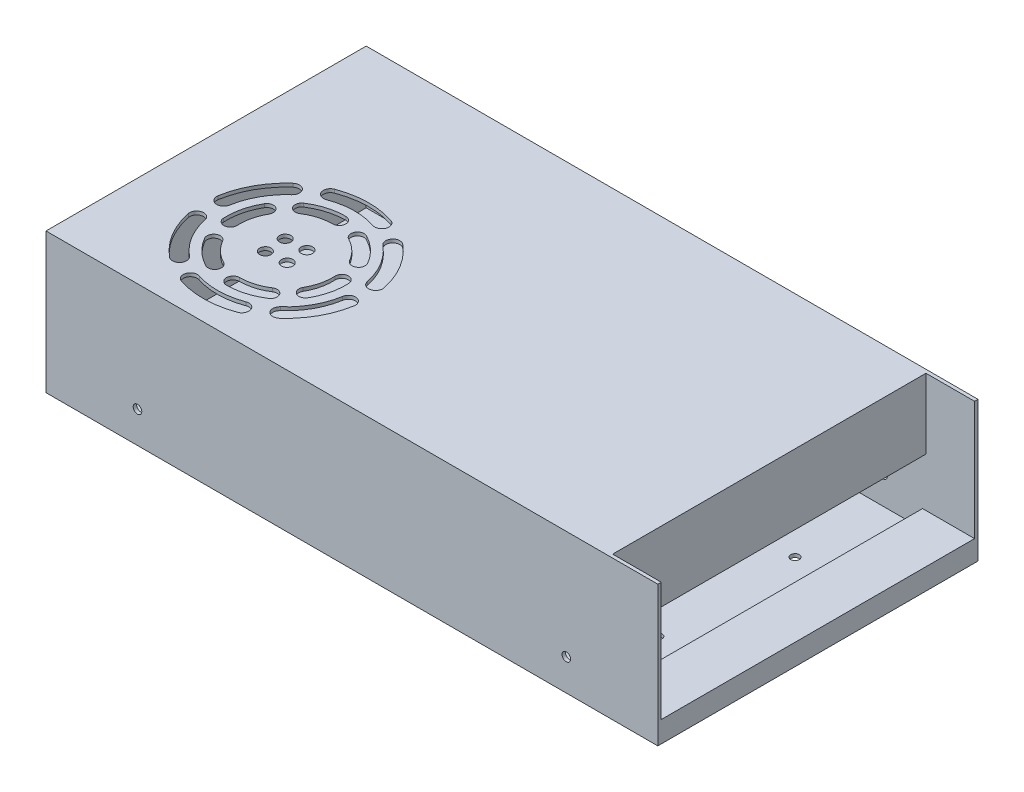
SolidWorks part; units mm, degrees
ref_plane "Front Plane" through (0, 0, 0) normal (0, 0, 1) x (1, 0, 0)
ref_plane "Top Plane" through (0, 0, 0) normal (0, 1, 0) x (1, 0, 0)
ref_plane "Right Plane" through (0, 0, 0) normal (1, 0, 0) x (0, 0, -1)
sketch "Sketch1" plane through (0, 0, 0) normal (0, 1, 0) x (1, 0, 0)
  line L1 (-107, 56) -> (107, 56)
  line L2 (-107, 56) -> (-107, -56)
  line L3 (-107, -56) -> (107, -56)
  line L4 (107, 56) -> (107, -56)
  line L5 (-107, 56) -> (107, -56) construction
  line L6 (-107, -56) -> (107, 56) construction
  point P0 (0, 0)
  dimension "D1" = 214
  dimension "D2" = 112
extrude "Boss-Extrude1" add sketch "Sketch1" along normal blind 49
sketch "Sketch2" plane through (0, 49, 0) normal (0, 1, 0) x (1, 0, 0)
  line L0 (107, -56) -> (107, 56) construction
  line L1 (107, 54.8) -> (88.8, 54.8)
  line L2 (107, 54.8) -> (107, -54.8)
  line L3 (107, -54.8) -> (88.8, -54.8)
  line L4 (88.8, 54.8) -> (88.8, -54.8)
  line L5 (107, 56) -> (-107, 56) construction
  line L6 (-107, -56) -> (107, -56) construction
  dimension "D1" = 18.2
  dimension "D2" = 1.2
  dimension "D3" = 1.2
extrude "Cut-Extrude1" cut sketch "Sketch2" against normal offset from surface (41.6 mm away) 7.4 up to face at (0, 0, 0)
shell "Shell1" thickness 1.2 removed face at (88.8, 28.2, 0)
sketch "Sketch3" plane through (0, 0, 56) normal (0, 0, 1) x (1, 0, 0)
  line L0 (-107, 0) -> (107, 0) construction
  line L1 (107, 49) -> (107, 0) construction
  line L3 (-107, 49) -> (-107, 0) construction
  circle A0 centre (75, 11) radius 1.5
  circle A1 centre (-75, 11) radius 1.5
  dimension "D1" = 3
  dimension "D4" = 3
  dimension "D2" = 11
  dimension "D3" = 32
  dimension "D5" = 11
  dimension "D6" = 32
extrude "Cut-Extrude2" cut sketch "Sketch3" against normal blind 10
sketch "Sketch4" plane through (0, 0, -56) normal (0, 0, -1) x (-1, 0, 0)
  line L0 (-107, 0) -> (107, 0) construction
  line L1 (-107, 49) -> (-107, 0) construction
  line L2 (107, 49) -> (107, 0) construction
  line L3 (-107, 49) -> (107, 49) construction
  circle A0 centre (-75, 11) radius 1.5
  circle A1 centre (-75, 36) radius 1.5
  circle A2 centre (75, 36) radius 1.5
  circle A3 centre (75, 11) radius 1.5
  dimension "D2" = 3
  dimension "D4" = 32
  dimension "D6" = 3
  dimension "D11" = 3
  dimension "D12" = 3
  dimension "D1" = 11
  dimension "D3" = 32
  dimension "D5" = 11
  dimension "D7" = 13
  dimension "D8" = 32
  dimension "D9" = 13
  dimension "D10" = 32
extrude "Cut-Extrude3" cut sketch "Sketch4" against normal blind 10
sketch "Sketch5" plane through (88.8, 0, 0) normal (1, 0, 0) x (0, 0, -1)
  line L0 (54.8, 47.8) -> (54.8, 1.2) construction
  line L1 (-54.8, 49) -> (54.8, 49)
  line L2 (-54.8, 49) -> (-54.8, 24.5)
  line L3 (-54.8, 24.5) -> (54.8, 24.5)
  line L4 (54.8, 49) -> (54.8, 24.5)
extrude "Boss-Extrude2" add sketch "Sketch5" along normal blind 1.2
sketch "Sketch6" plane through (0, 49, 0) normal (0, 1, 0) x (1, 0, 0)
  line L0 (-107, -56) -> (107, -56) construction
  line L1 (-107, 56) -> (-107, -56) construction
  arc A3 (-67.3347, -45.1552) -> (-49.6905, -44.8109) centre (-59, -20) ccw construction
  arc A4 (-68.1117, -47.5004) -> (-48.8226, -47.1241) centre (-59, -20) ccw
  arc A5 (-66.5576, -42.8099) -> (-50.5584, -42.4978) centre (-59, -20) ccw
  arc A6 (-66.5576, -42.8099) -> (-68.1117, -47.5004) centre (-67.3347, -45.1552) ccw
  arc A7 (-48.8226, -47.1241) -> (-50.5584, -42.4978) centre (-49.6905, -44.8109) ccw
  arc A8 (-84.9529, -25.3601) -> (-75.8327, -40.4682) centre (-59.0005, -20.0005) ccw construction
  arc A9 (-87.3725, -25.8597) -> (-77.402, -42.3765) centre (-59.0005, -20.0005) ccw
  arc A10 (-82.5333, -24.8604) -> (-74.2634, -38.56) centre (-59.0005, -20.0005) ccw
  arc A11 (-82.5333, -24.8604) -> (-87.3725, -25.8597) centre (-84.9529, -25.3601) ccw
  arc A12 (-77.402, -42.3765) -> (-74.2634, -38.56) centre (-75.8327, -40.4682) ccw
  arc A13 (-76.6189, -0.2046) -> (-85.1429, -15.657) centre (-59.0012, -20.0003) ccw construction
  arc A14 (-78.2614, 1.6409) -> (-87.5801, -15.2521) centre (-59.0012, -20.0003) ccw
  arc A15 (-74.9764, -2.0502) -> (-82.7057, -16.062) centre (-59.0012, -20.0003) ccw
  arc A16 (-74.9764, -2.0502) -> (-78.2614, 1.6409) centre (-76.6189, -0.2046) ccw
  arc A17 (-87.5801, -15.2521) -> (-82.7057, -16.062) centre (-85.1429, -15.657) ccw
  arc A18 (-50.6667, 5.1556) -> (-68.3109, 4.8114) centre (-59.0014, -19.9996) ccw construction
  arc A19 (-49.8897, 7.5009) -> (-69.1788, 7.1246) centre (-59.0014, -19.9996) ccw
  arc A20 (-51.4438, 2.8104) -> (-67.4429, 2.4982) centre (-59.0014, -19.9996) ccw
  arc A21 (-51.4438, 2.8104) -> (-49.8897, 7.5009) centre (-50.6667, 5.1556) ccw
  arc A22 (-69.1788, 7.1246) -> (-67.4429, 2.4982) centre (-68.3109, 4.8114) ccw
  arc A23 (-33.0485, -14.6395) -> (-42.1687, 0.4687) centre (-59.0008, -19.9991) ccw construction
  arc A24 (-30.6289, -14.1398) -> (-40.5994, 2.3769) centre (-59.0008, -19.9991) ccw
  arc A25 (-35.468, -15.1392) -> (-43.738, -1.4396) centre (-59.0008, -19.9991) ccw
  arc A26 (-35.468, -15.1392) -> (-30.6289, -14.1398) centre (-33.0485, -14.6395) ccw
  arc A27 (-40.5994, 2.3769) -> (-43.738, -1.4396) centre (-42.1687, 0.4687) ccw
  arc A28 (-41.3824, -39.7949) -> (-32.8585, -24.3425) centre (-59.0001, -19.9993) ccw construction
  arc A29 (-39.7399, -41.6405) -> (-30.4213, -24.7474) centre (-59.0001, -19.9993) ccw
  arc A30 (-43.025, -37.9493) -> (-35.2957, -23.9376) centre (-59.0001, -19.9993) ccw
  arc A31 (-43.025, -37.9493) -> (-39.7399, -41.6405) centre (-41.3824, -39.7949) ccw
  arc A32 (-30.4213, -24.7474) -> (-35.2957, -23.9376) centre (-32.8585, -24.3425) ccw
  arc A34 (-59.0008, -38.56) -> (-48.8989, -35.5702) centre (-59.0008, -19.9991) ccw construction
  arc A35 (-59.0008, -40.8668) -> (-47.6434, -37.5054) centre (-59.0008, -19.9991) ccw
  arc A36 (-59.0008, -36.2531) -> (-50.1544, -33.6349) centre (-59.0008, -19.9991) ccw
  arc A37 (-59.0008, -36.2531) -> (-59.0008, -40.8668) centre (-59.0008, -38.56) ccw
  arc A38 (-47.6434, -37.5054) -> (-50.1544, -33.6349) centre (-48.8989, -35.5702) ccw
  arc A39 (-75.075, -29.2795) -> (-67.4348, -36.5331) centre (-59.0008, -19.9991) ccw construction
  arc A40 (-77.0728, -30.433) -> (-68.483, -38.5881) centre (-59.0008, -19.9991) ccw
  arc A41 (-73.0773, -28.1261) -> (-66.3866, -34.4782) centre (-59.0008, -19.9991) ccw
  arc A42 (-73.0773, -28.1261) -> (-77.0728, -30.433) centre (-75.075, -29.2795) ccw
  arc A43 (-68.483, -38.5881) -> (-66.3866, -34.4782) centre (-67.4348, -36.5331) ccw
  arc A44 (-75.075, -10.7186) -> (-77.5367, -20.9621) centre (-59.0008, -19.9991) ccw construction
  arc A45 (-77.0728, -9.5652) -> (-79.8405, -21.0817) centre (-59.0008, -19.9991) ccw
  arc A46 (-73.0773, -11.872) -> (-75.233, -20.8424) centre (-59.0008, -19.9991) ccw
  arc A47 (-73.0773, -11.872) -> (-77.0728, -9.5652) centre (-75.075, -10.7186) ccw
  arc A48 (-79.8405, -21.0817) -> (-75.233, -20.8424) centre (-77.5367, -20.9621) ccw
  arc A49 (-59.0008, -1.4382) -> (-69.1027, -4.428) centre (-59.0008, -19.9991) ccw construction
  arc A50 (-59.0008, 0.8687) -> (-70.3583, -2.4927) centre (-59.0008, -19.9991) ccw
  arc A51 (-59.0008, -3.745) -> (-67.8472, -6.3633) centre (-59.0008, -19.9991) ccw
  arc A52 (-59.0008, -3.745) -> (-59.0008, 0.8687) centre (-59.0008, -1.4382) ccw
  arc A53 (-70.3583, -2.4927) -> (-67.8472, -6.3633) centre (-69.1027, -4.428) ccw
  arc A54 (-42.9266, -10.7186) -> (-50.5668, -3.465) centre (-59.0008, -19.9991) ccw construction
  arc A55 (-40.9288, -9.5652) -> (-49.5186, -1.4101) centre (-59.0008, -19.9991) ccw
  arc A56 (-44.9244, -11.872) -> (-51.6151, -5.5199) centre (-59.0008, -19.9991) ccw
  arc A57 (-44.9244, -11.872) -> (-40.9288, -9.5652) centre (-42.9266, -10.7186) ccw
  arc A58 (-49.5186, -1.4101) -> (-51.6151, -5.5199) centre (-50.5668, -3.465) ccw
  arc A59 (-42.9266, -29.2795) -> (-40.4649, -19.0361) centre (-59.0008, -19.9991) ccw construction
  arc A60 (-40.9288, -30.433) -> (-38.1612, -18.9164) centre (-59.0008, -19.9991) ccw
  arc A61 (-44.9244, -28.1261) -> (-42.7686, -19.1558) centre (-59.0008, -19.9991) ccw
  arc A62 (-44.9244, -28.1261) -> (-40.9288, -30.433) centre (-42.9266, -29.2795) ccw
  arc A63 (-38.1612, -18.9164) -> (-42.7686, -19.1558) centre (-40.4649, -19.0361) ccw
  circle A64 centre (-55.1922, -23.4597) radius 1.998
  circle A65 centre (-62.4615, -23.8077) radius 1.998
  circle A66 centre (-62.8094, -16.5384) radius 1.998
  circle A67 centre (-55.5402, -16.1905) radius 1.998
  point P12 (-58.4831, -46.495)
  point P17 (-53.7333, -37.7968)
  point P20 (-81.6874, -33.6956)
  point P28 (-82.205, -7.2004)
  point P36 (-59.5183, 6.4954)
  point P44 (-36.314, -6.3039)
  point P52 (-35.7964, -32.7991)
  point P57 (-59.0007, -19.9998)
  point P66 (-71.7804, -33.4598)
  point P73 (-77.0479, -15.662)
  point P80 (-64.2684, -2.2013)
  point P87 (-46.2213, -6.5384)
  point P94 (-40.9537, -24.3361)
  point P99 (-59.0008, -19.9991)
  point P109 (-59.0008, -19.9991)
  dimension "D2" = 6
  dimension "D1" = 36
  dimension "D3" = 48
  dimension "D5" = 4
extrude "Cut-Extrude5" cut sketch "Sketch6" against normal blind 10
sketch "Sketch7" plane through (0, 0, 0) normal (0, -1, 0) x (1, 0, 0)
  line L0 (107, 56) -> (107, -56) construction
  line L1 (107, -56) -> (-107, -56) construction
  line L2 (-107, 56) -> (107, 56) construction
  line L3 (-107, -56) -> (-107, 56) construction
  circle A0 centre (-75, 24) radius 1.5
  circle A1 centre (75, 24) radius 1.5
  circle A2 centre (75, -24) radius 1.5
  circle A3 centre (-75, -24) radius 1.5
  dimension "D1" = 3
  dimension "D2" = 3
  dimension "D7" = 3
  dimension "D10" = 3
  dimension "D3" = 32
  dimension "D4" = 32
  dimension "D5" = 32
  dimension "D6" = 32
  dimension "D8" = 32
  dimension "D9" = 32
  dimension "D11" = 32
  dimension "D12" = 32
extrude "Cut-Extrude6" cut sketch "Sketch7" against normal blind 10
